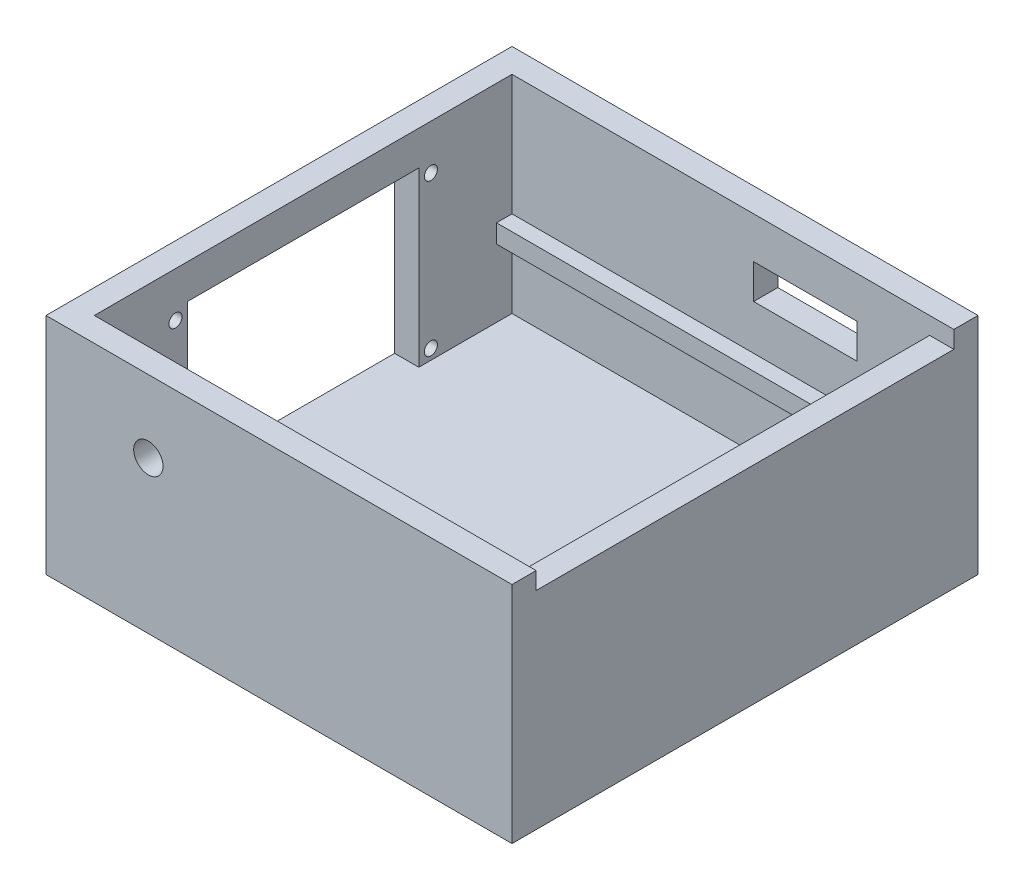
SolidWorks part; units mm, degrees
ref_plane "Front Plane" through (0, 0, 0) normal (0, 0, 1) x (1, 0, 0)
ref_plane "Top Plane" through (0, 0, 0) normal (0, 1, 0) x (1, 0, 0)
ref_plane "Right Plane" through (0, 0, 0) normal (1, 0, 0) x (0, 0, -1)
sketch "Sketch2" plane through (0, 0, 0) normal (0, 1, 0) x (1, 0, 0)
  line L0 (-60.5, 60.5) -> (-60.5, -60.5)
  line L1 (-67.5, 67.5) -> (67.5, 67.5)
  line L2 (-67.5, 67.5) -> (-67.5, -67.5)
  line L3 (-67.5, -67.5) -> (67.5, -67.5)
  line L4 (67.5, 67.5) -> (67.5, -67.5)
  line L5 (-67.5, 67.5) -> (67.5, -67.5) construction
  line L6 (-67.5, -67.5) -> (67.5, 67.5) construction
  line L7 (-60.5, -60.5) -> (60.5, -60.5)
  line L8 (60.5, 60.5) -> (60.5, -60.5)
  line L9 (-60.5, 60.5) -> (60.5, 60.5)
  point P0 (0, 0)
  dimension "D1" = 135
  dimension "D2" = 135
  dimension "D3" = 7
extrude "Boss-Extrude1" add sketch "Sketch2" along normal blind 65
extrude "Boss-Extrude2" add sketch "Sketch2<2>" along normal blind 5 contours L9 L0 L7 L8 region at (0, 0, 0)
sketch "Sketch2<2>" plane through (0, 0, 0) normal (0, 1, 0) x (1, 0, 0) same geometry as "Sketch2"
sketch "Sketch3" plane through (0, 0, -60.5) normal (0, 0, 1) x (1, 0, 0)
  line L1 (0, 0) -> (0, 65) construction
  line L2 (67.5, 0) -> (-67.5, 0) construction
  line L3 (60.5, 65) -> (-60.5, 65) construction
  line L4 (60.5, 65) -> (60.5, 5) construction
  line L5 (-60.5, 24.6663) -> (60.5, 24.6663)
  line L6 (-60.5, 24.6663) -> (-60.5, 30)
  line L7 (-60.5, 30) -> (60.5, 30)
  line L8 (60.5, 24.6663) -> (60.5, 30)
  line L9 (-60.5, 24.6663) -> (60.5, 30) construction
  line L10 (-60.5, 30) -> (60.5, 24.6663) construction
  line L11 (-60.5, 5) -> (60.5, 5) construction
  line L12 (-60.5, 65) -> (-60.5, 5) construction
  line L13 (9.5, 53) -> (39.5, 53)
  line L14 (9.5, 53) -> (9.5, 43)
  line L15 (9.5, 43) -> (39.5, 43)
  line L16 (39.5, 53) -> (39.5, 43)
  line L17 (9.5, 53) -> (39.5, 43) construction
  line L18 (9.5, 43) -> (39.5, 53) construction
  point P1 (0, 27.3332)
  point P16 (24.5, 48)
  point P23 (0, 0)
  dimension "D1" = 25
  dimension "D2" = 121
  dimension "D3" = 30
  dimension "D4" = 10
  dimension "D5" = 70
  dimension "D6" = 13
extrude "Boss-Extrude3" add sketch "Sketch3" along normal blind 4.5 contours L5 L8 L7 L6
extrude "Cut-Extrude1" cut sketch "Sketch3<3>" against normal through all contours L16 L13 L14 L15 region at (24.5, 48, -60.5)
sketch "Sketch3<3>" plane through (0, 0, -60.5) normal (0, 0, 1) x (1, 0, 0) same geometry as "Sketch3"
sketch "Sketch10" plane through (0, 0, 67.5) normal (0, 0, 1) x (1, 0, 0)
  circle A0 centre (-37.8514, 44.0831) radius 4.25
extrude "Cut-Extrude2" cut sketch "Sketch10" against normal blind 26.5 contours A0
sketch "Sketch11" plane through (-67.5, 0, 0) normal (-1, 0, 0) x (0, 0, 1)
  line L1 (-40, 5) -> (40, 5)
  line L2 (-40, 5) -> (-40, 55)
  line L3 (-40, 55) -> (40, 55)
  line L4 (40, 5) -> (40, 55)
  line L5 (-40, 5) -> (40, 55) construction
  line L6 (-40, 55) -> (40, 5) construction
  line L7 (-33.5, 55) -> (33.5, 55)
  line L8 (-33.5, 55) -> (-33.5, 5)
  line L9 (-33.5, 5) -> (33.5, 5)
  line L14 (0, 0) -> (0, 60) construction
  line L15 (-67.5, 0) -> (67.5, 0) construction
  line L16 (-67.5, 65) -> (67.5, 65) construction
  line L17 (0, 30) -> (67.5, 30) construction
  line L18 (67.5, 65) -> (67.5, 0) construction
  line L19 (33.5, 55) -> (33.5, 5)
  circle A0 centre (-37, 52) radius 1.9
  circle A1 centre (37, 52) radius 1.9
  circle A2 centre (37, 8) radius 1.9
  circle A3 centre (-37, 8) radius 1.9
  point P0 (0, 30)
  point P23 (0, 0)
  dimension "D2" = 3.8
  dimension "D3" = 3.5
  dimension "D1" = 3.5
extrude "Cut-Extrude3" cut sketch "Sketch11" against normal blind 26.5 contours L8 L7 L19 L9 | A0 | A2 | A1 | A3
sketch "Sketch12" plane through (0, 65, 0) normal (0, 1, 0) x (1, 0, 0)
  line L0 (67.5, -67.5) -> (67.5, 67.5) construction
  line L1 (60.5, 60.5) -> (67.5, 60.5)
  line L2 (60.5, 60.5) -> (60.5, -60.5)
  line L3 (60.5, -60.5) -> (67.5, -60.5)
  line L4 (67.5, 60.5) -> (67.5, -60.5)
extrude "Cut-Extrude4" cut sketch "Sketch12" against normal blind 5
